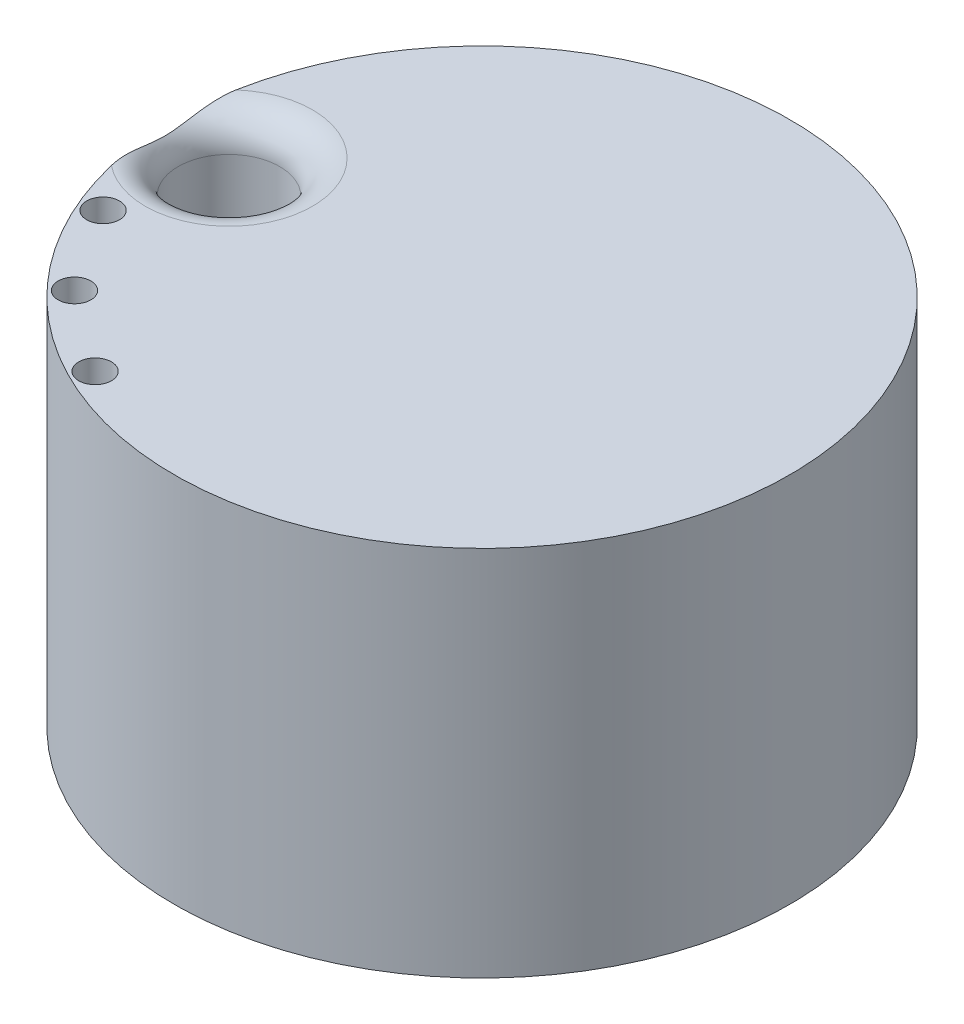
SolidWorks part; units mm, degrees
ref_plane "Front Plane" through (0, 0, 0) normal (0, 0, 1) x (1, 0, 0)
ref_plane "Top Plane" through (0, 0, 0) normal (0, 1, 0) x (1, 0, 0)
ref_plane "Right Plane" through (0, 0, 0) normal (1, 0, 0) x (0, 0, -1)
sketch "Sketch2" plane through (0, 0, 0) normal (0, 1, 0) x (1, 0, 0)
  circle A0 centre (0, 0) radius 47.6885
  dimension "D1" = 95.377
extrude "Boss-Extrude1" add sketch "Sketch2" along normal blind 57.658
sketch "Sketch4" plane through (0, 57.658, 0) normal (0, 1, 0) x (1, 0, 0)
  circle A1 centre (-26.162, 0) radius 3.175
  circle A2 centre (26.162, 0) radius 3.175
  circle A3 centre (0, 26.162) radius 3.175
  circle A4 centre (0, -26.162) radius 3.175
  point P0 (0, 0)
sketch "Sketch5" plane through (0, 57.658, 0) normal (0, 1, 0) x (1, 0, 0)
  line L0 (0, 0) -> (-32.4801, -30.672)
  line L1 (0, 0) -> (-41.0118, -17.7134)
  line L2 (0, 0) -> (-20.0308, -39.9311)
  line L3 (-46.1552, -0.9403) -> (-47.6792, -0.9403)
  circle A1 centre (-41.0118, -17.7134) radius 2.54
  circle A2 centre (0, 0) radius 44.6736
  circle A3 centre (-32.4801, -30.672) radius 2.54
  circle A4 centre (-20.0308, -39.9311) radius 2.54
  circle A8 centre (0, 0) radius 47.6885 construction
  circle A9 centre (-38.2812, -0.9403) radius 7.874
  point P7 (0, 0)
  point P8 (0, 0)
  dimension "D1" = 20
  dimension "D2" = 20
extrude "Cut-Extrude5" cut sketch "Sketch5" against normal through all contours A4 | A3 | A9 | A1
fillet "Fillet3" radius 5.08 2 edges at (-38.2812, 57.658, 8.8143) (-38.2812, 0, 8.8143)
